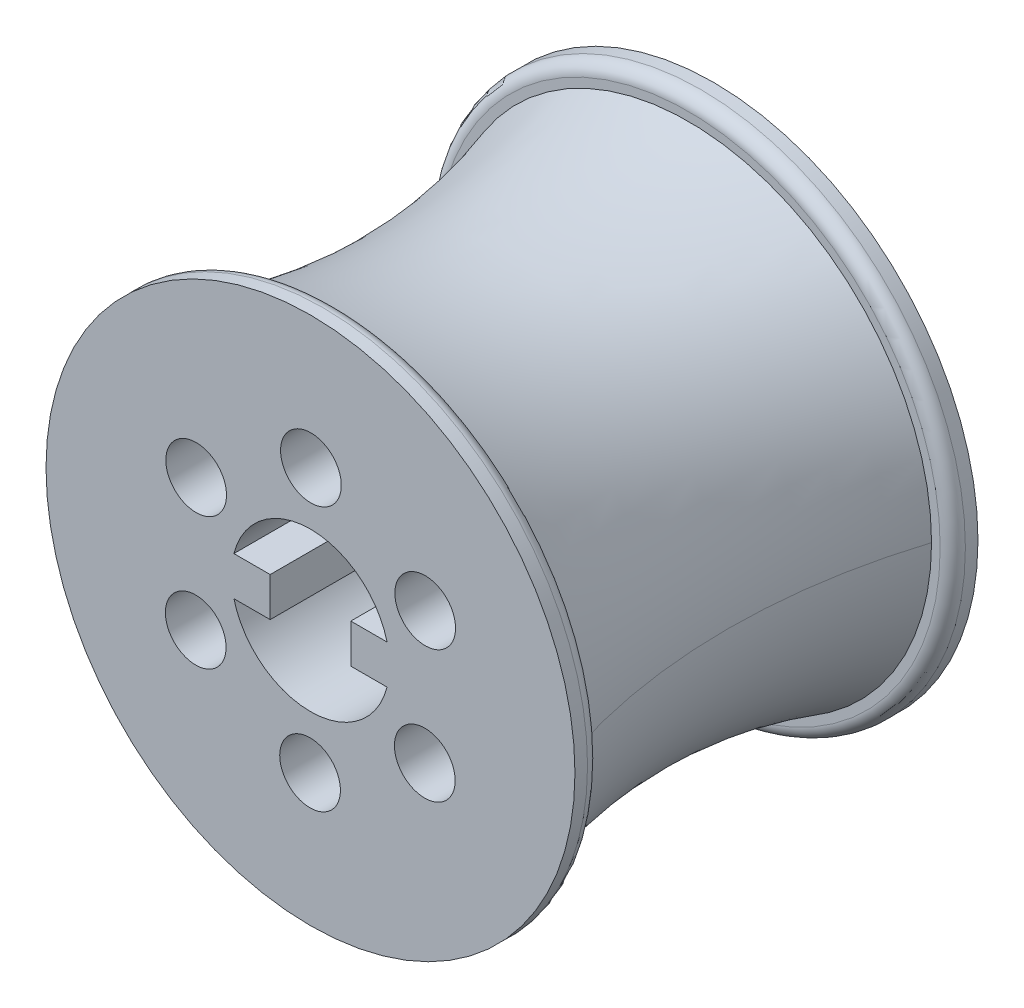
SolidWorks part; units mm, degrees
ref_plane "Front Plane" through (0, 0, 0) normal (0, 0, 1) x (1, 0, 0)
ref_plane "Top Plane" through (0, 0, 0) normal (0, 1, 0) x (1, 0, 0)
ref_plane "Right Plane" through (0, 0, 0) normal (1, 0, 0) x (0, 0, -1)
sketch "Sketch3" plane through (0, 0, 0) normal (0, 0, 1) x (1, 0, 0)
  circle A0 centre (0, 0) radius 21
  dimension "D1" = 42
extrude "Boss-Extrude3" add sketch "Sketch3" along normal blind 32
sketch "Sketch4" plane through (0, 0, 32) normal (0, 0, 1) x (1, 0, 0)
  circle A0 centre (0, 0) radius 19.3127
  circle A1 centre (0, 0) radius 21
extrude "Cut-Extrude1" cut sketch "Sketch4" against normal blind 28 from offset 2 offset against normal yes
ref_plane "Plane2" through (0, 0, 16) normal (0, 0, -1) x (-1, 0, 0)
ref_plane "Plane3" through (0, 0, 0) normal (0, 1, 0) x (1, 0, 0)
sketch "Sketch7" plane through (0, 0, 0) normal (0, 1, 0) x (1, 0, 0)
  line L0 (-19.3127, -2) -> (-19.3127, -30)
  arc A2 (-19.3127, -2) -> (-19.3127, -30) centre (-63.469, -16) cw
ref_axis "Axis1" through (0, 0, 2) along (0, 0, 1)
sweep "Cut-Sweep1" cut profiles "Sketch7" path edge at (19.3127, 0, 2)
sketch "Sketch8" plane through (0, 0, 0) normal (0, 0, -1) x (-1, 0, 0)
  line L0 (0, 6.075) -> (0, 17) construction
  line L1 (-4.6154, 10.5) -> (4.5477, 10.5) construction
  line L2 (17.6, 0) -> (-17.6, 0) construction
  circle A0 centre (0, 0) radius 6.075
  circle A1 centre (9.0763, 5.2793) radius 2.4097
  circle A2 centre (-0.0339, 10.5) radius 2.4097
  circle A3 centre (0, 0) radius 17 construction
  circle A4 centre (9.1102, -5.2207) radius 2.4097
  circle A5 centre (0.0339, -10.5) radius 2.4097
  circle A6 centre (-9.0763, -5.2793) radius 2.4097
  circle A7 centre (-9.1102, 5.2207) radius 2.4097
  dimension "D1" = 12.15
  dimension "D3" = 34
  dimension "D2" = 10.5
  dimension "D4" = 6
extrude "Cut-Extrude2" cut sketch "Sketch8" against normal through all contours A7 | A2 | A1 | A4 | A5 | A6 | A0
sketch "Sketch9" plane through (0, 0, 0) normal (0, 0, -1) x (-1, 0, 0)
  circle A0 centre (0, 0) radius 17
  circle A1 centre (0, 0) radius 4
  dimension "D1" = 34
sketch "Sketch10" plane through (0, 0, 0) normal (0, 1, 0) x (1, 0, 0)
  line L0 (-6.075, 0) -> (-15.2418, -2.7958)
  line L1 (-15.2418, -2.7958) -> (-19.075, 0)
  line L2 (17, 0) -> (-17, 0) construction
  line L3 (21, 0) -> (-21, 0) construction
  line L4 (-19.075, 0) -> (-6.075, 0)
  dimension "D1" = 13
revolve "Cut-Revolve1" cut sketch "Sketch10" angle 360 about axis through (0, 0, 2) along (0, 0, 1)
fillet "Fillet1" radius 1 2 edges at (21, 0, 30) (21, 0, 2)
fillet "Fillet3" radius 5 1 edges at (-15.2418, 0, 2.7958)
sketch "Sketch11" plane through (0, 0, 32) normal (0, 0, 1) x (1, 0, 0)
  circle A0 centre (0, 0) radius 8
  dimension "D1" = 16
extrude "Boss-Extrude4" add sketch "Sketch11" against normal blind 15 from offset 17 offset against normal yes
sketch "Sketch12" plane through (0, 0, 32) normal (0, 0, 1) x (1, 0, 0)
  line L0 (-3, -1.75) -> (-9.25, -1.75)
  line L1 (9.25, 1.75) -> (3, 1.75)
  line L2 (9.25, 1.75) -> (9.25, -1.75)
  line L3 (9.25, -1.75) -> (3, -1.75)
  line L4 (-9.25, 1.75) -> (-9.25, -1.75)
  line L5 (-3, 1.75) -> (-9.25, 1.75)
  line L8 (-3, 1.75) -> (-3, -1.75)
  line L10 (3, 1.75) -> (3, -1.75)
  point P0 (0, 0)
  point P6 (0, 0)
  dimension "D1" = 18.5
  dimension "D2" = 3.5
extrude "Boss-Extrude5" add sketch "Sketch12" against normal up to surface (17 mm away) up to face at (6.075, 0, 15)
sketch "Sketch15" plane through (0, 0, 32) normal (0, 0, 1) x (1, 0, 0)
  line L5 (-6.0806, 1.55) -> (-3.2, 1.55)
  line L6 (-3.2, 1.55) -> (-3.2, -1.55)
  line L11 (-3.2, -1.55) -> (-6.0806, -1.55)
  line L12 (6.0806, -1.55) -> (3.2, -1.55)
  line L13 (3.2, -1.55) -> (3.2, 1.55)
  line L14 (3.2, 1.55) -> (6.0806, 1.55)
  line L28 (-6.2079, 1.45) -> (-3.3, 1.45)
  line L29 (-3.3, 1.45) -> (-3.3, -1.45)
  line L30 (-3.3, -1.45) -> (-6.2079, -1.45)
  line L31 (6.2079, -1.45) -> (3.3, -1.45)
  line L32 (3.3, -1.45) -> (3.3, 1.45)
  line L33 (3.3, 1.45) -> (6.2079, 1.45)
  line L34 (-6.2079, 1.45) -> (-3.3, 1.45) construction
  line L35 (-3.3, 1.45) -> (-3.3, -1.45) construction
  line L36 (-3.3, -1.45) -> (-6.2079, -1.45) construction
  line L37 (6.2079, -1.45) -> (3.3, -1.45) construction
  line L38 (3.3, -1.45) -> (3.3, 1.45) construction
  line L39 (3.3, 1.45) -> (6.2079, 1.45) construction
  arc A2 (-6.0806, -1.55) -> (6.0806, -1.55) centre (0, 0) ccw
  arc A3 (6.0806, 1.55) -> (-6.0806, 1.55) centre (0, 0) ccw
  circle A5 centre (0, 0) radius 21
  circle A6 centre (0, 0) radius 21
  arc A10 (-6.2079, -1.45) -> (6.2079, -1.45) centre (0, 0) ccw
  arc A11 (6.2079, 1.45) -> (-6.2079, 1.45) centre (0, 0) ccw
  arc A12 (-6.2079, -1.45) -> (6.2079, -1.45) centre (0, 0) ccw construction
  arc A13 (6.2079, 1.45) -> (-6.2079, 1.45) centre (0, 0) ccw construction
  dimension "D1" = 0
  dimension "D2" = 0.3
  dimension "D3" = 0.1
extrude "Cut-Extrude3" cut sketch "Sketch15" against normal up to surface (17 mm away) flip side to cut up to face at (0, 0, 15)
